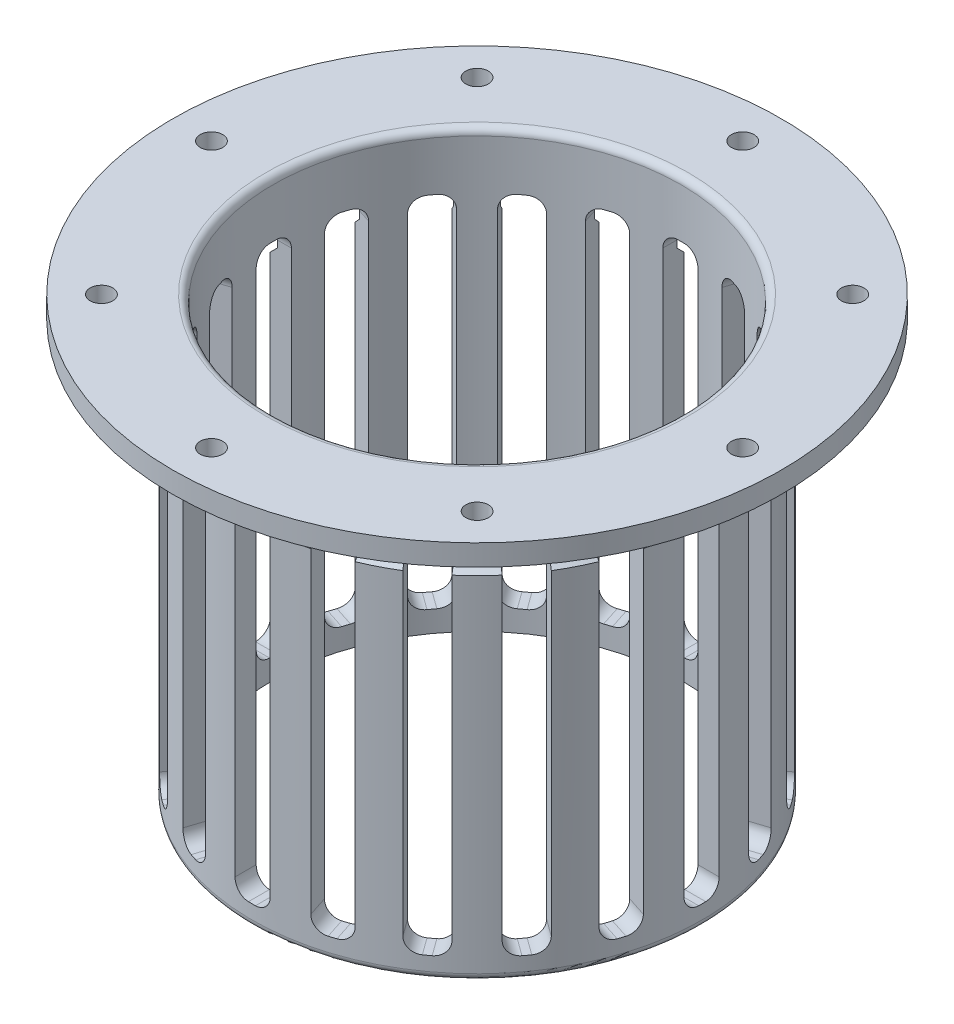
SolidWorks part; units mm, degrees
ref_plane "Front Plane" through (0, 0, 0) normal (0, 0, 1) x (1, 0, 0)
ref_plane "Top Plane" through (0, 0, 0) normal (0, 1, 0) x (1, 0, 0)
ref_plane "Right Plane" through (0, 0, 0) normal (1, 0, 0) x (0, 0, -1)
sketch "Sketch1" plane through (0, 0, 0) normal (0, 1, 0) x (1, 0, 0)
  circle A0 centre (0, 0) radius 32
  circle A1 centre (0, 0) radius 43.25
  circle A2 centre (0, 0) radius 37.75 construction
  circle A3 centre (0, 37.75) radius 1.6
  circle A4 centre (26.6933, 26.6933) radius 1.6
  circle A5 centre (37.75, 0) radius 1.6
  circle A6 centre (26.6933, -26.6933) radius 1.6
  circle A7 centre (0, -37.75) radius 1.6
  circle A8 centre (-26.6933, -26.6933) radius 1.6
  circle A9 centre (-37.75, 0) radius 1.6
  circle A10 centre (-26.6933, 26.6933) radius 1.6
  circle A11 centre (0, 0) radius 45.25 construction
  point P23 (0, 0)
  dimension "D1" = 64
  dimension "D2" = 86.5
  dimension "D3" = 3.2
  dimension "D5" = 90.5
  dimension "D6" = 7.5
  dimension "D4" = 8
extrude "Boss-Extrude1" add sketch "Sketch1" along normal blind 3
sketch "Sketch2" plane through (0, 0, 0) normal (0, -1, 0) x (1, 0, 0)
  circle A0 centre (0, 0) radius 32
  circle A1 centre (0, 0) radius 32 construction
  circle A2 centre (0, 0) radius 29
  dimension "D1" = 3
extrude "Boss-Extrude2" add sketch "Sketch2" along normal blind 5 and the other way up to surface (3 mm away) other way up to face at (-37.75, 3, 1.6)
sketch "Sketch3" plane through (0, -5, 0) normal (0, -1, 0) x (1, 0, 0)
  circle A0 centre (0, 0) radius 29
  circle A1 centre (0, 0) radius 31
  circle A2 centre (0, 0) radius 29 construction
  dimension "D1" = 2
extrude "Boss-Extrude3" add sketch "Sketch3" along normal blind 4
sketch "Sketch4" plane through (0, -9, 0) normal (0, -1, 0) x (1, 0, 0)
  circle A0 centre (0, 0) radius 29
  circle A1 centre (0, 0) radius 32
  circle A2 centre (0, 0) radius 32 construction
  circle A3 centre (0, 0) radius 29 construction
extrude "Boss-Extrude4" add sketch "Sketch4" along normal blind 50
sketch "Sketch5" plane through (0, 0, 0) normal (1, 0, 0) x (0, 0, -1)
  line L0 (-31, -5) -> (31, -5) construction
  line L1 (-2.5, -5) -> (2.5, -5)
  line L2 (-2.5, -5) -> (-2.5, -56)
  line L3 (-2.5, -56) -> (2.5, -56)
  line L4 (2.5, -5) -> (2.5, -56)
  line L5 (0, 0) -> (0, -59) construction
  line L6 (-32, -59) -> (32, -59) construction
  point P11 (0, -56)
  dimension "D1" = 5
  dimension "D2" = 3
extrude "Cut-Extrude1" cut sketch "Sketch5" against normal blind 50
fillet "Fillet1" radius 2 4 edges at (-30.3971, -56, -2.5) (-30.3971, -56, 2.5) (-29.8955, -5, -2.5) (-29.8955, -5, 2.5)
pattern_circular "CirPattern1" count 20 over 360 about axis through (0, 0, 0) along (0, 1, 0) of "Fillet1", "Cut-Extrude1"
fillet "Fillet2" radius 1 2 edges at (0, 0, 32) (0, 3, 29)
chamfer "Chamfer1" distance 1 angle 45 20 edges at (27.6212, -9, -14.0737) (21.9203, -9, -21.9203) (14.0737, -9, -27.6212) (4.8495, -9, -30.6183) (-4.8495, -9, -30.6183) (30.6183, -9, -4.8495) (30.6183, -9, 4.8495) (27.6212, -9, 14.0737) (21.9203, -9, 21.9203) (14.0737, -9, 27.6212) (4.8495, -9, 30.6183) (-4.8495, -9, 30.6183) (-14.0737, -9, 27.6212) (-21.9203, -9, 21.9203) (-27.6212, -9, 14.0737) (-30.6183, -9, 4.8495) (-30.6183, -9, -4.8495) (-27.6212, -9, -14.0737) (-21.9203, -9, -21.9203) (-14.0737, -9, -27.6212)
fillet "Fillet3" radius 1 1 edges at (0, -59, -32)
